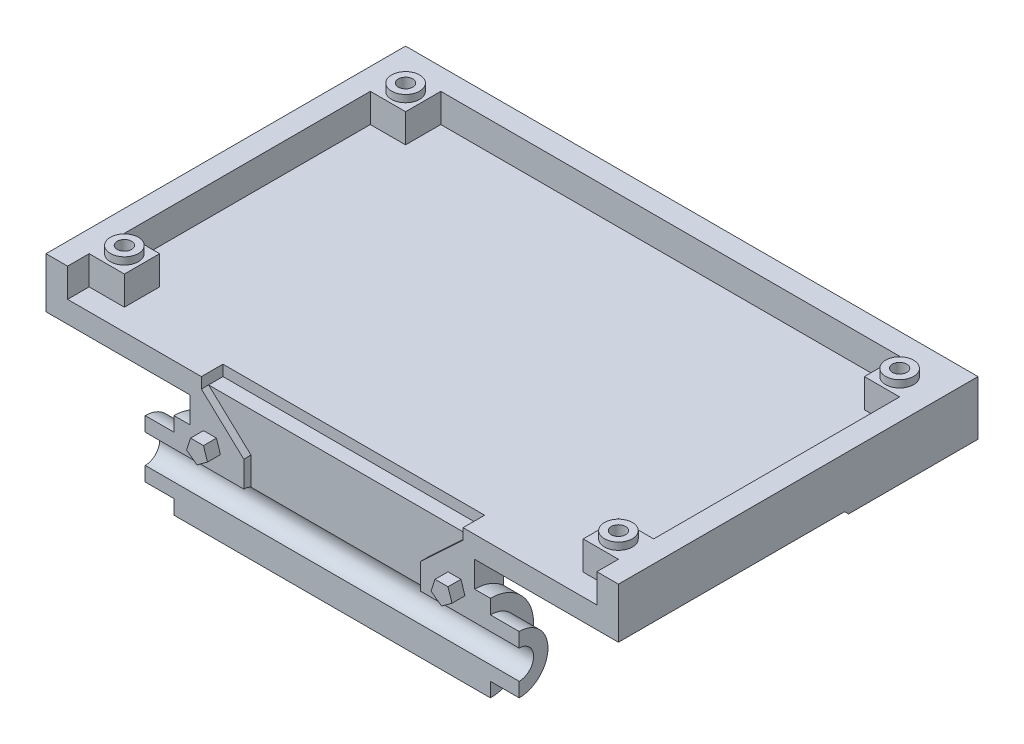
SolidWorks part; units mm, degrees
ref_plane "Ön Düzlem" through (0, 0, 0) normal (0, 0, 1) x (1, 0, 0)
ref_plane "Üst Düzlem" through (0, 0, 0) normal (0, 1, 0) x (1, 0, 0)
ref_plane "Sağ Düzlem" through (0, 0, 0) normal (1, 0, 0) x (0, 0, -1)
sketch "Çizim2" plane through (0, 0, 0) normal (0, 0, 1) x (1, 0, 0)
  line L1 (-47.2438, 23.3082) -> (-7.2438, 23.3082)
  line L2 (-47.2438, 23.3082) -> (-47.2438, 7.3082)
  line L3 (-47.2438, 7.3082) -> (-7.2438, 7.3082)
  line L4 (-7.2438, 23.3082) -> (-7.2438, 7.3082)
extrude "Yükseklik-Ekstrüzyon4" add sketch "Çizim2" along normal blind 9
sketch "Çizim3" plane through (-7.2438, 0, 0) normal (1, 0, 0) x (0, 0, -1)
  line L0 (-9, 7.3082) -> (-9, 23.3082) construction
  line L1 (-9, 21.3082) -> (-9, 9.3082)
  arc A0 (-9, 11.3082) -> (-9, 19.3082) centre (-9, 15.3082) ccw
  arc A1 (-9, 9.3082) -> (-9, 21.3082) centre (-9, 15.3082) ccw
  line M1 (0, 7.3082) -> (0, 23.3082)
  line M2 (0, 23.3082) -> (-9, 23.3082)
  line M3 (-9, 23.3082) -> (-9, 7.3082)
  line M4 (-9, 7.3082) -> (0, 7.3082)
extrude "Yükseklik-Ekstrüzyon5" add sketch "Çizim3" along normal blind 2 and the other way blind 42 contours A1 L1 A0 M3 region at (-7.2438, 15.3082, 3.1342)
extrude "Yükseklik-Ekstrüzyon6" add sketch "Çizim3<3>" along normal blind 6 and the other way blind 46 contours L1 A0 region at (-7.2438, 15.3082, 7.3023)
sketch "Çizim3<3>" plane through (-7.2438, 0, 0) normal (1, 0, 0) x (0, 0, -1) same geometry as "Çizim3"
sketch "Çizim4" plane through (-1.2438, 0, 0) normal (1, 0, 0) x (0, 0, -1)
  line L0 (-9, 17.3082) -> (-9, 13.3082)
  arc A3 (-9, 13.3082) -> (-9, 17.3082) centre (-9, 15.3082) ccw
extrude "Kes-Ekstrüzyon1" cut sketch "Çizim4" against normal blind 52
extrude "Kes-Ekstrüzyon2" cut sketch "Çizim3<4>" against normal blind 52 and the other way through all contours A1 L1 M4 M1 M2 M3 region at (-7.2438, 22.3082, 8.8164)
sketch "Çizim3<4>" plane through (-7.2438, 0, 0) normal (1, 0, 0) x (0, 0, -1) same geometry as "Çizim3"
sketch "Çizim7" plane through (-5.2438, 0, 0) normal (1, 0, 0) x (0, 0, -1)
  line L0 (-5, 19.7803) -> (-5, 24.3082)
  line L3 (-9, 21.3082) -> (-9, 24.3082)
  line L4 (-9, 24.3082) -> (-5, 24.3082)
  arc A1 (-9, 21.3082) -> (-5, 19.7803) centre (-9, 15.3082) cw
extrude "Yükseklik-Ekstrüzyon7" add sketch "Çizim7" against normal blind 44
sketch "Çizim8" plane through (0, 0, 9) normal (0, 0, 1) x (1, 0, 0)
  line L0 (-7.4438, 24.3082) -> (-7.4438, 21.3082)
  line L1 (-49.2438, 24.3082) -> (-47.0438, 24.3082)
  line L2 (-49.2438, 24.3082) -> (-49.2438, 22.3082)
  line L5 (-5.2438, 24.3082) -> (-7.4438, 24.3082)
  line L6 (-5.2438, 24.3082) -> (-5.2438, 22.3082)
  line L9 (-7.4438, 21.3082) -> (-5.2438, 21.3082)
  line L10 (-5.2438, 24.3082) -> (-5.2438, 19.3082) construction
  line L11 (-5.2438, 21.3082) -> (-5.2438, 22.3082)
  line L12 (-47.0438, 24.3082) -> (-47.0438, 21.3082)
  line L13 (-47.0438, 21.3082) -> (-49.2438, 21.3082)
  line L14 (-49.2438, 24.3082) -> (-49.2438, 19.3082) construction
  line L15 (-49.2438, 21.3082) -> (-49.2438, 22.3082)
extrude "Kes-Ekstrüzyon4" cut sketch "Çizim8" against normal blind 44 contours L6 L11 L9 L0 L5 | L2 L15 L13 L12 L1
sketch "Çizim10" plane through (-5.2438, 0, 0) normal (1, 0, 0) x (0, 0, -1)
  line L1 (-9, 21.3082) -> (-5, 21.3082)
  line L2 (-5, 21.3082) -> (-5, 19.7803)
  arc A0 (-9, 21.3082) -> (-5, 19.7803) centre (-9, 15.3082) cw
extrude "Kes-Ekstrüzyon8" cut sketch "Çizim7<3>" against normal blind 2.2 contours A1 L0 L4 L3
sketch "Çizim7<3>" plane through (-5.2438, 0, 0) normal (1, 0, 0) x (0, 0, -1) same geometry as "Çizim7"
sketch "Çizim12" plane through (-49.2438, 0, 0) normal (-1, 0, 0) x (0, 0, 1)
  line L0 (5, 19.7803) -> (5, 21.3082)
  line L1 (5, 21.3082) -> (9, 21.3082)
  arc A0 (5, 19.7803) -> (9, 21.3082) centre (9, 15.3082) cw
extrude "Kes-Ekstrüzyon9" cut sketch "Çizim12" against normal blind 2.2
sketch "Çizim14" plane through (0, 24.3082, 0) normal (0, 1, 0) x (1, 0, 0)
  line L0 (-47.0438, -5) -> (-47.0438, -9) construction
  line L1 (-7.4438, -9) -> (-47.0438, -9)
  line L2 (-7.4438, -9) -> (-7.4438, -6)
  line L3 (-7.4438, -6) -> (-47.0438, -6)
  line L4 (-47.0438, -9) -> (-47.0438, -6)
extrude "aralik_eks" add sketch "Çizim14" along normal blind 0.6
sketch "Çizim15" plane through (0, 24.9082, 0) normal (0, 1, 0) x (1, 0, 0)
  line L0 (-53.2438, -9) -> (-49.2438, -9) construction
  line L1 (-47.0438, -6) -> (-67.0438, -6)
  line L3 (-47.0438, -9) -> (-67.0438, -9)
  line L4 (-67.0438, -6) -> (-67.0438, -9)
  line L5 (-7.4438, -9) -> (-5.2438, -9) construction
  line L6 (-7.4438, -6) -> (12.5562, -6)
  line L8 (-7.4438, -9) -> (12.5562, -9)
  line L9 (12.5562, -6) -> (12.5562, -9)
  line L10 (-47.0438, -9) -> (-7.4438, -9)
  line L11 (-7.4438, -6) -> (-47.0438, -6)
extrude "Yükseklik-Ekstrüzyon9" add sketch "Çizim15" along normal blind 7
sketch "Çizim16" plane through (0, 0, 6) normal (0, 0, -1) x (-1, 0, 0)
  line L0 (-12.5562, 24.9082) -> (-12.5562, 31.9082)
  line L2 (67.0438, 31.9082) -> (67.0438, 24.9082)
  line L8 (-12.5562, 24.9082) -> (67.0438, 24.9082)
  line L14 (-9.5562, 27.9082) -> (-9.5562, 31.9082)
  line L15 (-9.5562, 27.9082) -> (64.0438, 27.9082)
  line L16 (64.0438, 31.9082) -> (64.0438, 27.9082)
  line L17 (-12.5562, 31.9082) -> (-9.5562, 31.9082)
  line L18 (64.0438, 31.9082) -> (67.0438, 31.9082)
extrude "Yükseklik-Ekstrüzyon11" add sketch "Çizim16" along normal blind 47
sketch "Çizim17" plane through (0, 0, 6) normal (0, 0, -1) x (-1, 0, 0)
  line L1 (-9.5562, 31.9082) -> (64.0438, 31.9082)
  line L2 (-9.5562, 31.9082) -> (-9.5562, 27.9082)
  line L3 (-9.5562, 27.9082) -> (64.0438, 27.9082)
  line L4 (64.0438, 31.9082) -> (64.0438, 27.9082)
extrude "Kes-Ekstrüzyon10" cut sketch "Çizim17" against normal blind 10
sketch "Çizim18" plane through (0, 27.9082, 0) normal (0, 1, 0) x (1, 0, 0)
  line L0 (-64.0438, 41) -> (9.5562, 41)
  line L1 (-64.0438, 41) -> (-64.0438, 38)
  line L2 (-64.0438, 38) -> (9.5562, 38)
  line L3 (9.5562, 41) -> (9.5562, 38)
  line L4 (-64.0438, 38) -> (-59.1438, 38)
  line L5 (-64.0438, 38) -> (-64.0438, 33.1)
  line L6 (-64.0438, 33.1) -> (-59.1438, 33.1)
  line L7 (-59.1438, 38) -> (-59.1438, 33.1)
  line L8 (4.6562, 38) -> (9.5562, 38)
  line L9 (4.6562, 38) -> (4.6562, 33.1)
  line L10 (4.6562, 33.1) -> (9.5562, 33.1)
  line L11 (9.5562, 38) -> (9.5562, 33.1)
  line L12 (4.6562, -1.1) -> (9.5562, -1.1)
  line L13 (4.6562, -1.1) -> (4.6562, -6)
  line L14 (4.6562, -6) -> (9.5562, -6)
  line L15 (9.5562, -1.1) -> (9.5562, -6)
  line L16 (-64.0438, -1.1) -> (-59.1438, -1.1)
  line L17 (-64.0438, -1.1) -> (-64.0438, -6)
  line L18 (-64.0438, -6) -> (-59.1438, -6)
  line L19 (-59.1438, -1.1) -> (-59.1438, -6)
  circle A0 centre (-61.5938, 35.55) radius 1
  circle A1 centre (-61.5938, 35.55) radius 1.95
  circle A2 centre (-61.5938, -3.55) radius 1
  circle A3 centre (-61.5938, -3.55) radius 1.95
  circle A4 centre (7.1062, -3.55) radius 1
  circle A5 centre (7.1062, -3.55) radius 1.95
  circle A6 centre (7.1062, 35.55) radius 1
  circle A7 centre (7.1062, 35.55) radius 1.95
  line M1 (-64.0438, 41) -> (-64.0438, -9)
  line M3 (9.5562, -9) -> (9.5562, 41)
  line M4 (9.5562, 41) -> (-64.0438, 41)
extrude "Yükseklik-Ekstrüzyon12" add sketch "Çizim18" along normal blind 4 contours L9 L10 L2 A7 M3 | L7 L2 L6 A1 M1 | L2 M1 M3 M4 | L19 L16 L18 A3 M1 | L13 L14 L12 A5 M3 region at (9.4869, 27.9082, 3.55) region at (-61.5938, 27.9082, 1.1693) region at (-27.2438, 27.9082, -39.5) region at (-61.5938, 27.9082, -37.9307) region at (9.4869, 27.9082, -35.55)
extrude "Yükseklik-Ekstrüzyon13" add sketch "Çizim18<3>" along normal blind 5 contours A1 A0 | A7 A6 | A5 A4 | A3 A2 region at (-63.4886, 27.9082, -35.55) region at (-63.4886, 27.9082, 3.55) region at (5.2114, 27.9082, 3.55) region at (5.2114, 27.9082, -35.55)
sketch "Çizim18<3>" plane through (0, 27.9082, 0) normal (0, 1, 0) x (1, 0, 0) same geometry as "Çizim18"
extrude "Kes-Ekstrüzyon11" cut sketch "Çizim18<4>" against normal blind 7 contours A2 | A0 | A6 | A4 region at (-61.5938, 27.9082, -35.55) region at (-61.5938, 27.9082, 3.55) region at (7.1062, 27.9082, 3.55) region at (7.1062, 27.9082, -35.55)
sketch "Çizim18<4>" plane through (0, 27.9082, 0) normal (0, 1, 0) x (1, 0, 0) same geometry as "Çizim18"
sketch "Çizim19" plane through (0, 0, 9) normal (0, 0, 1) x (1, 0, 0)
  line L0 (-39.5438, 20.9082) -> (-39.5438, 15.0341)
  line L3 (-47.0438, 27.9082) -> (-7.4438, 27.9082)
  line L7 (-39.5438, 20.9082) -> (-47.0438, 27.9082)
  line L8 (-14.9438, 20.9082) -> (-7.4438, 27.9082)
  line L9 (-14.9438, 20.9082) -> (-14.9438, 15.0341)
  line L11 (-64.0438, 27.9082) -> (9.5562, 27.9082)
  line L13 (-39.5438, 15.0341) -> (-14.9438, 15.0341)
  line L16 (-45.4366, 26.4082) -> (-9.0509, 26.4082)
  point P1 (0, 0)
  line M35 (9.5562, 27.9082) -> (-64.0438, 27.9082)
  line M45 (-53.2438, 17.3082) -> (-1.2438, 17.3082)
ref_plane "Düzlem3" through (-47.0438, 21.3082, 9) normal (-1, 0, 0) x (0, 0, 1)
extrude "Kes-Ekstrüzyon12" cut sketch "Çizim19" against normal blind 1 contours L9 L8 L7 L0 M35 M45 | L0 L13 L9 M45 region at (-27.2438, 22.2018, 9) region at (-27.2438, 16.1711, 9)
sketch "Çizim21" plane through (0, 0, 9) normal (0, 0, 1) x (1, 0, 0)
  line L0 (-45.4366, 26.4082) -> (-45.4366, 27.9082)
  line L1 (-59.1438, 27.9082) -> (4.6562, 27.9082) construction
  line L2 (-45.4366, 27.9082) -> (-9.0509, 27.9082)
  line L3 (-9.0509, 27.9082) -> (-9.0509, 26.4082)
  line L4 (-9.0509, 26.4082) -> (-45.4366, 26.4082)
extrude "Kes-Ekstrüzyon13" cut sketch "Çizim21" against normal blind 3
sketch "Çizim22" plane through (0, 0, 9) normal (0, 0, 1) x (1, 0, 0)
  line L0 (-27.2438, 17.0403) -> (-27.2438, 21.9749)
  line L2 (-39.5438, 17.0403) -> (-14.9438, 17.0403) construction
  line L3 (-10.2438, 18.777) -> (-8.7875, 19.8351)
  line L4 (-8.7875, 19.8351) -> (-9.3438, 21.547)
  line L5 (-9.3438, 21.547) -> (-11.1438, 21.547)
  line L6 (-11.1438, 21.547) -> (-11.7, 19.8351)
  line L7 (-11.7, 19.8351) -> (-10.2438, 18.777)
  line L8 (-42.7875, 19.8351) -> (-44.2438, 18.777)
  line L9 (-43.3438, 21.547) -> (-42.7875, 19.8351)
  line L10 (-45.1438, 21.547) -> (-43.3438, 21.547)
  line L11 (-45.7, 19.8351) -> (-45.1438, 21.547)
  line L12 (-44.2438, 18.777) -> (-45.7, 19.8351)
extrude "Yükseklik-Ekstrüzyon14" add sketch "Çizim22" along normal blind 1.8 contours L12 L8 L9 L10 L11 | L6 L7 L3 L4 L5 region at (-10.2438, 20.3082, 9) region at (-44.2438, 20.3082, 9)
sketch "Çizim23" plane through (0, 24.9082, 0) normal (0, -1, 0) x (1, 0, 0)
  line L1 (-67.0438, -41) -> (12.5562, -41)
  line L2 (-67.0438, -41) -> (-67.0438, -22)
  line L4 (12.5562, -41) -> (12.5562, -22)
  line L6 (11.5562, -40) -> (11.5562, -22)
  line L7 (-66.0438, -40) -> (11.5562, -40)
  line L8 (-66.0438, -40) -> (-66.0438, -22)
  line L9 (-67.0438, -21) -> (12.5562, -21) construction
  line L10 (-66.0438, -22) -> (11.5562, -22) construction
  line L11 (-66.0438, -22) -> (-67.0438, -22)
  line L12 (-67.0438, -41) -> (-67.0438, -21) construction
  line L13 (11.5562, -22) -> (12.5562, -22)
  line L14 (12.5562, -41) -> (12.5562, -21) construction
extrude "Yükseklik-Ekstrüzyon15" add sketch "Çizim23" along normal blind 0.55
chamfer "Pah1" distance 1 angle 45 2 edges at (12.0562, 24.3582, -22) (-66.5438, 24.3582, -22)
